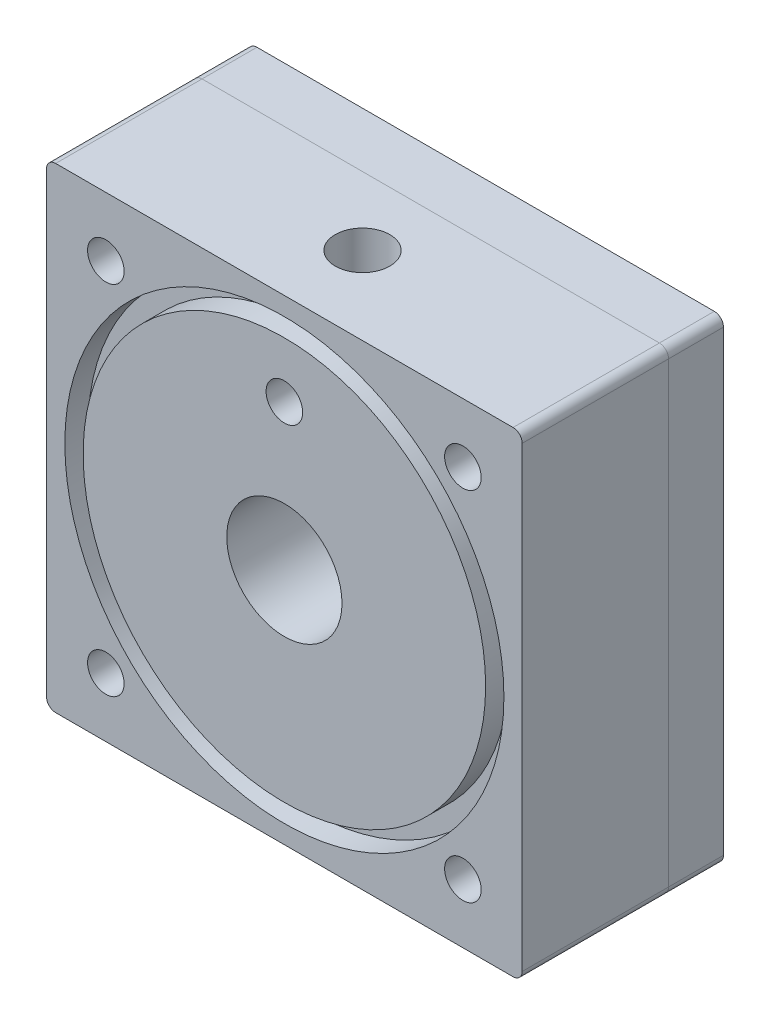
SolidWorks part; units mm, degrees
ref_plane "Front Plane" through (0, 0, 0) normal (0, 0, 1) x (1, 0, 0)
ref_plane "Top Plane" through (0, 0, 0) normal (0, 1, 0) x (1, 0, 0)
ref_plane "Right Plane" through (0, 0, 0) normal (1, 0, 0) x (0, 0, -1)
sketch "Sketch1" plane through (0, 0, 0) normal (0, 0, 1) x (1, 0, 0)
  line L1 (-82.55, 82.55) -> (82.55, 82.55)
  line L2 (-82.55, 82.55) -> (-82.55, -82.55)
  line L3 (-82.55, -82.55) -> (82.55, -82.55)
  line L4 (82.55, 82.55) -> (82.55, -82.55)
  line L5 (-82.55, 82.55) -> (82.55, -82.55) construction
  line L6 (-82.55, -82.55) -> (82.55, 82.55) construction
  circle A0 centre (0, 0) radius 32
  circle A1 centre (0, 0) radius 30
  circle A2 centre (0, 0) radius 20
  circle A3 centre (0, 0) radius 40
  circle A4 centre (0, 0) radius 87.63 construction
  circle A5 centre (-61.9638, 61.9638) radius 6.35
  circle A6 centre (61.9638, 61.9638) radius 6.35
  circle A7 centre (61.9638, -61.9638) radius 6.35
  circle A8 centre (-61.9638, -61.9638) radius 6.35
  point P0 (0, 0)
  point P23 (0, 0)
  dimension "D2" = 80
  dimension "D3" = 40
  dimension "D4" = 60
  dimension "D5" = 64
  dimension "D6" = 175.26
  dimension "D7" = 12.7
  dimension "D1" = 165.1
  dimension "D8" = 4
extrude "Boss-Extrude1" add sketch "Sketch1" against normal blind 102.8 contours A3 A0 region at (-38.8686, 0, 0)
extrude "Boss-Extrude2" add sketch "Sketch1<3>" against normal blind 82.8 contours A0 A1 region at (-31.0949, 0, 0)
sketch "Sketch1<3>" plane through (0, 0, 0) normal (0, 0, 1) x (1, 0, 0) same geometry as "Sketch1"
extrude "Boss-Extrude3" add sketch "Sketch1<4>" against normal blind 60.8 contours A1 A2 region at (-29.1515, 0, 0)
sketch "Sketch1<4>" plane through (0, 0, 0) normal (0, 0, 1) x (1, 0, 0) same geometry as "Sketch1"
extrude "Boss-Extrude4" add sketch "Sketch1<5>" against normal blind 50.8 contours L4 L1 L2 L3 A8 A7 A6 A5 A3 region at (0, 80.2151, 0)
sketch "Sketch1<5>" plane through (0, 0, 0) normal (0, 0, 1) x (1, 0, 0) same geometry as "Sketch1"
sketch "Sketch2" plane through (0, 0, 0) normal (0, 0, 1) x (1, 0, 0)
  circle A0 centre (0, 0) radius 69.85
  circle A1 centre (0, 0) radius 76.2
  dimension "D1" = 139.7
  dimension "D2" = 152.4
extrude "Cut-Extrude1" cut sketch "Sketch2" against normal blind 8
hole_wizard "Ø1.0mm Dowel Hole1" positions "Sketch3" profile "Sketch4" hole size "Ø1.0" standard "ANSI Metric"
sketch "Sketch3" plane through (0, 82.55, 0) normal (0, 1, 0) x (1, 0, 0)
  line L0 (-82.55, 0) -> (82.55, 0) construction
  point P0 (0, 27.1204)
  point P5 (0, 0)
  dimension "D1" = 27.1204
sketch "Sketch4" plane through (0, 82.55, -27.1204) normal (1, 0, 0) x (0, 0, 1)
  line L0 (0, 0) -> (0, 52.7162)
  line L1 (0, 52.7162) -> (9.485, 47.24)
  line L2 (9.485, 47.24) -> (9.485, 0)
  line L5 (9.485, 0) -> (0, 0)
  line L10 (0, 52.7162) -> (-9.485, 47.24) construction
  line L11 (0, -6.35) -> (0, 107.95) construction
  dimension "Hole Dia." = 18.97
  dimension "Hole Depth" = 47.24
  dimension "Drill Angle" = 120
cosmetic thread "Cosmetic Thread1" parameters "D1"=41.91, "D2"=22
hole_wizard "Ø1.5mm Dowel Hole1" positions "Sketch6" profile "Sketch7" hole size "Ø1.5" standard "ANSI Metric" end condition up to next
sketch "Sketch6" plane through (0, 0, 0) normal (0, 0, 1) x (1, 0, 0)
  line L0 (-82.55, 82.55) -> (82.55, 82.55) construction
  point P0 (0, 50.55)
  point P2 (0, 0)
  dimension "D1" = 32
sketch "Sketch7" plane through (0, 50.55, 0) normal (1, 0, 0) x (0, -1, 0)
  line L0 (0, 0) -> (0, 17.6354)
  line L1 (0, 17.6354) -> (6.35, 17.6354)
  line L2 (6.35, 17.6354) -> (6.35, 0)
  line L5 (6.35, 0) -> (0, 0)
  line L11 (0, -6.35) -> (0, 107.95) construction
  dimension "Thru Hole Dia." = 12.7
  dimension "Thru Hole Depth" = 17.6354
sketch "Sketch8" plane through (0, 0, -50.8) normal (0, 0, -1) x (-1, 0, 0)
  line L4 (-82.55, 82.55) -> (-82.55, -82.55)
  line L5 (-82.55, -82.55) -> (82.55, -82.55)
  line L6 (82.55, -82.55) -> (82.55, 82.55)
  line L7 (82.55, 82.55) -> (-82.55, 82.55)
  line L8 (-82.55, 82.55) -> (-82.55, -82.55)
  line L9 (-82.55, -82.55) -> (82.55, -82.55)
  line L10 (82.55, -82.55) -> (82.55, 82.55)
  line L11 (82.55, 82.55) -> (-82.55, 82.55)
  circle A0 centre (61.9638, -61.9638) radius 6.35 construction
  circle A1 centre (-61.9638, -61.9638) radius 6.35 construction
  circle A2 centre (-61.9638, 61.9638) radius 6.35 construction
  circle A3 centre (61.9638, 61.9638) radius 6.35 construction
  circle A4 centre (61.9638, -61.9638) radius 6.35
  circle A5 centre (-61.9638, -61.9638) radius 6.35
  circle A6 centre (-61.9638, 61.9638) radius 6.35
  circle A7 centre (61.9638, 61.9638) radius 6.35
  dimension "D1" = 0
extrude "Boss-Extrude5" add sketch "Sketch8" along normal blind 19.05 separate body
fillet "Fillet1" radius 3.175 4 edges at (82.55, 82.55, -25.4) (-82.55, 82.55, -25.4) (82.55, -82.55, -25.4) (-82.55, -82.55, -25.4)
fillet "Fillet2" radius 3.175 4 edges at (-82.55, 82.55, -60.325) (82.55, -82.55, -60.325) (82.55, 82.55, -60.325) (-82.55, -82.55, -60.325)
